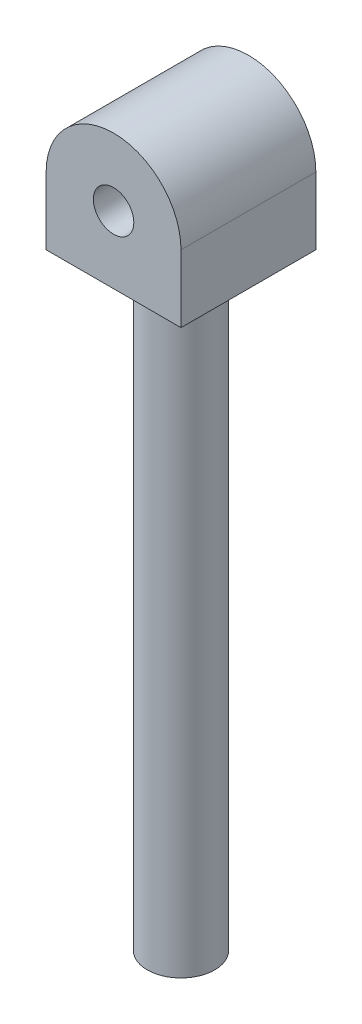
SolidWorks part; units mm, degrees
ref_plane "Alzado" through (0, 0, 0) normal (0, 0, 1) x (1, 0, 0)
ref_plane "Planta" through (0, 0, 0) normal (0, 1, 0) x (1, 0, 0)
ref_plane "Vista lateral" through (0, 0, 0) normal (1, 0, 0) x (0, 0, -1)
sketch "Croquis1" plane through (0, 0, 0) normal (0, 0, 1) x (1, 0, 0)
  line L0 (-5, 0) -> (-5, -5)
  line L1 (-5, -5) -> (5, -5)
  line L2 (5, -5) -> (5, 0)
  line L3 (0, 5) -> (-12.3649, 5) construction
  circle A0 centre (0, 0) radius 1.5
  arc A1 (5, 0) -> (-5, 0) centre (0, 0) ccw
  dimension "D1" = 3
  dimension "D2" = 10
  dimension "D3" = 10
extrude "Saliente-Extruir1" add sketch "Croquis1" along normal blind 10
sketch "Croquis2" plane through (0, -5, 0) normal (0, -1, 0) x (1, 0, 0)
  line L0 (-5, 5) -> (5, 5) construction
  line L1 (-5, 10) -> (-5, 0) construction
  line L2 (5, 10) -> (5, 0) construction
  circle A0 centre (0, 5) radius 2.5
  dimension "D1" = 5
extrude "Saliente-Extruir2" add sketch "Croquis2" along normal blind 45
ref_plane "Plano1" through (0, 0, 5) normal (0, 0, 1) x (1, 0, 0)
ref_axis "Eje1" through (0, 7, 5) along (0, -1, 0)
